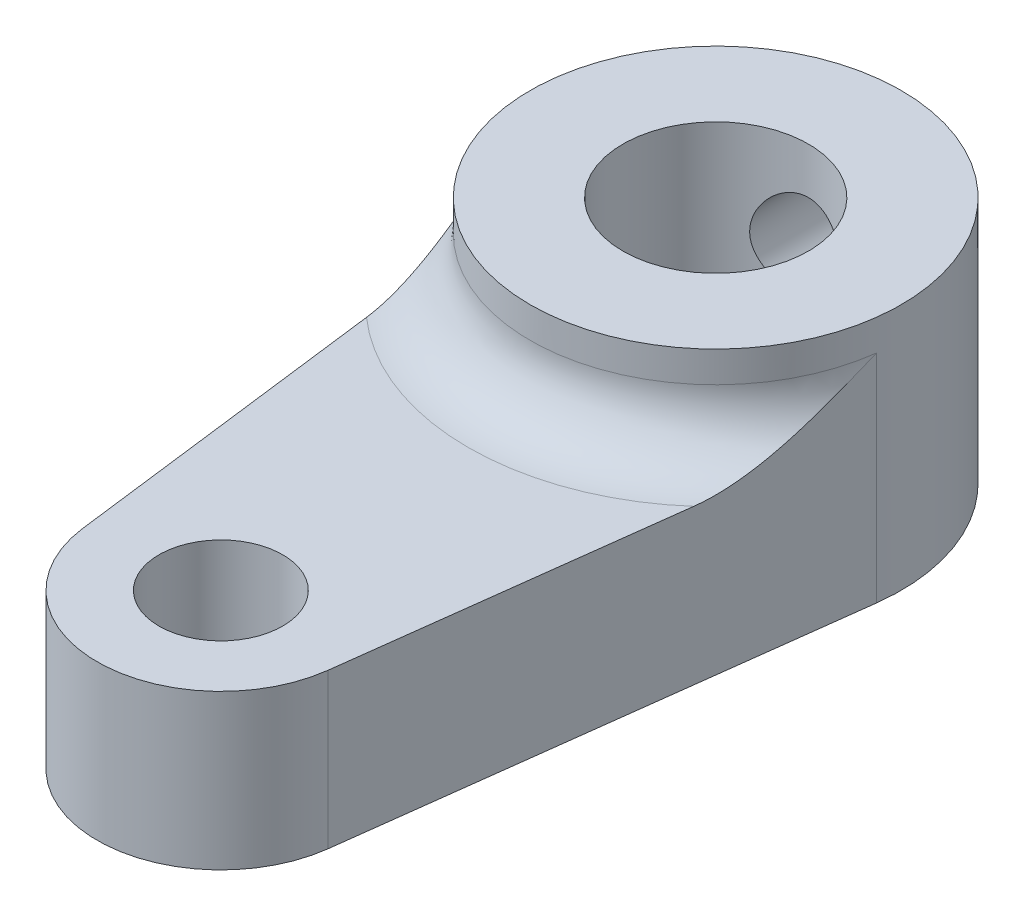
SolidWorks part; units mm, degrees
ref_plane "Front Plane" through (0, 0, 0) normal (0, 0, 1) x (1, 0, 0)
ref_plane "Top Plane" through (0, 0, 0) normal (0, 1, 0) x (1, 0, 0)
ref_plane "Right Plane" through (0, 0, 0) normal (1, 0, 0) x (0, 0, -1)
sketch "Sketch1" plane through (0, 0, 0) normal (0, 1, 0) x (1, 0, 0)
  line L0 (0, 0) -> (0, -16) construction
  line L1 (-5.9529, -0.75) -> (-3.9686, -16.5)
  line L2 (5.9529, -0.75) -> (3.9686, -16.5)
  circle A0 centre (0, 0) radius 6
  circle A1 centre (0, -16) radius 4
  circle A2 centre (0, -16) radius 2
  dimension "D1" = 4
  dimension "D2" = 8
  dimension "D3" = 12
  dimension "D4" = 16
extrude "Boss-Extrude1" add sketch "Sketch1" along normal blind 5
sketch "Sketch2" plane through (0, 5, 0) normal (0, 1, 0) x (1, 0, 0)
  circle A0 centre (0, 0) radius 6
extrude "Boss-Extrude2" add sketch "Sketch2" along normal blind 3
fillet "Fillet1" radius 2 1 edges at (0, 5, 6)
sketch "Sketch3" plane through (0, 8, 0) normal (0, 1, 0) x (1, 0, 0)
  circle A0 centre (0, 0) radius 3
  dimension "D1" = 6
extrude "Cut-Extrude1" cut sketch "Sketch3" against normal through all
sketch "Sketch4" plane through (0, 0, 0) normal (0, -1, 0) x (1, 0, 0)
  line L0 (-7.8303, -6.8263) -> (10.0206, -6.8263)
surface "Surface-Extrude1" sketch "Sketch4" parameters "D1"=8
hole_wizard "M3 Tapped Hole1" positions "Sketch5" profile "Sketch6" tap size "M3" standard "ISO"
sketch "Sketch5" plane through (0, 0, -6.8263) normal (0, 0, 1) x (1, 0, 0)
  line L0 (-7.8303, 0) -> (10.0206, 0) construction
  point P0 (0, 5)
  dimension "D1" = 5
sketch "Sketch6" plane through (0, 5, -6.8263) normal (1, 0, 0) x (0, 1, 0)
  line L0 (0, 0) -> (0, 9.4013)
  line L1 (0, 9.4013) -> (1.5, 8.5)
  line L2 (1.5, 8.5) -> (1.5, 0.025)
  line L3 (1.5, 0.025) -> (1.525, 0)
  line L5 (1.525, 0) -> (0, 0)
  line L6 (-1.5, 0.025) -> (-1.525, 0) construction
  line L10 (0, 9.4013) -> (-1.5, 8.5) construction
  line L11 (0, -6.35) -> (0, 107.95) construction
  dimension "Tap Drill Dia." = 3
  dimension "Tap Drill Depth" = 8.5
  dimension "Near C'Sink Dia." = 3.05
  dimension "Near C'Sink Angle" = 90
  dimension "Drill Angle" = 118
cosmetic thread "Hole Thread1" parameters "D1"=4.2282, "D2"=3
